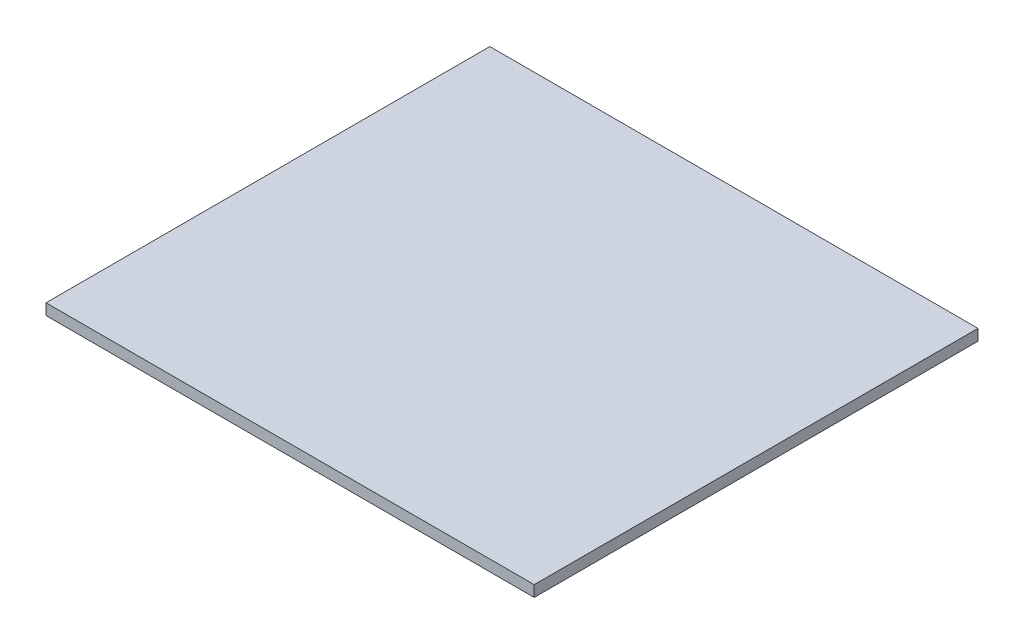
SolidWorks part; units mm, degrees
material "Corrugated Paper"
ref_plane "Front Plane" through (0, 0, 0) normal (0, 0, 1) x (1, 0, 0)
ref_plane "Top Plane" through (0, 0, 0) normal (0, 1, 0) x (1, 0, 0)
ref_plane "Right Plane" through (0, 0, 0) normal (1, 0, 0) x (0, 0, -1)
sketch "Sketch1" plane through (0, 0, 0) normal (0, 1, 0) x (1, 0, 0)
  line L1 (0, 0) -> (220, 0)
  line L2 (0, 0) -> (0, 200)
  line L3 (0, 200) -> (220, 200)
  line L4 (220, 0) -> (220, 200)
  dimension "D1" = 200
  dimension "D2" = 220
extrude "Boss-Extrude1" add sketch "Sketch1" along normal blind 5
